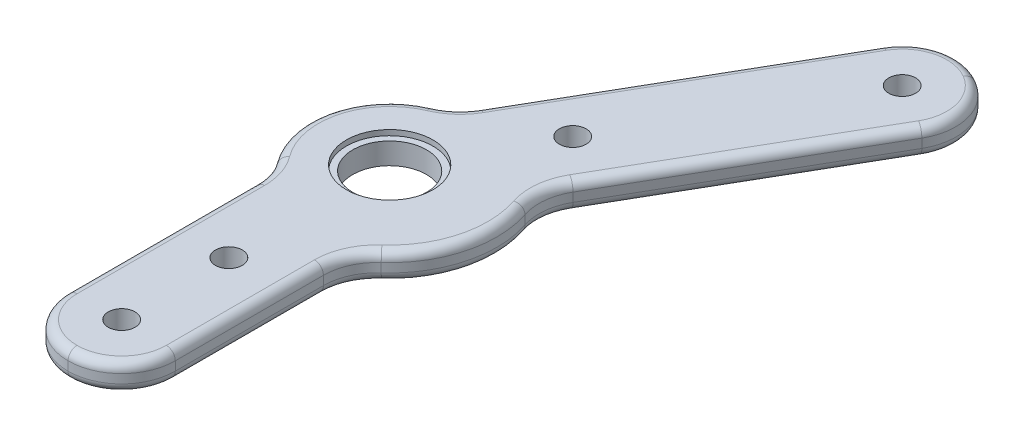
SolidWorks part; units mm, degrees
material "6061 Alloy"
ref_plane "Front Plane" through (0, 0, 0) normal (0, 0, 1) x (1, 0, 0)
ref_plane "Top Plane" through (0, 0, 0) normal (0, 1, 0) x (1, 0, 0)
ref_plane "Right Plane" through (0, 0, 0) normal (1, 0, 0) x (0, 0, -1)
sketch "Sketch1" plane through (0, 0, 0) normal (0, 1, 0) x (1, 0, 0)
  line L0 (0, 44.45) -> (0, -44.45) construction
  line L1 (-12.7, -44.45) -> (12.7, -44.45)
  line L2 (-12.7, -44.45) -> (-12.7, 31.75)
  line L3 (-12.7, 44.45) -> (12.7, 44.45) construction
  line L4 (12.7, -44.45) -> (12.7, 31.75)
  line L5 (-12.7, -44.45) -> (12.7, 44.45) construction
  line L6 (-12.7, 44.45) -> (12.7, -44.45) construction
  line L7 (0, 31.75) -> (50.8, 119.7382) construction
  line L8 (10.9985, 25.4) -> (61.7985, 113.3882)
  line L9 (61.7985, 113.3882) -> (39.8015, 126.0882)
  line L10 (39.8015, 126.0882) -> (-10.9985, 38.1)
  line L11 (-10.9985, 38.1) -> (10.9985, 25.4) construction
  line L12 (12.7, 44.45) -> (12.7, 31.75) construction
  line L13 (12.7, 44.45) -> (12.7, 79.147) construction
  circle A0 centre (0, 31.75) radius 12.7 construction
  circle A1 centre (0, -31.75) radius 3.175
  circle A2 centre (0, -6.35) radius 3.175
  circle A3 centre (0, 31.75) radius 8.7312
  circle A4 centre (44.45, 108.7397) radius 3.175
  circle A5 centre (15.875, 59.2463) radius 3.175
  circle A6 centre (0, 31.75) radius 19.05
  arc A7 (21.997, 44.45) -> (12.7, 9.753) centre (0, 31.75) cw
  point P0 (0, 0)
  point P16 (50.8, 119.7382)
  point P21 (0, 31.75)
  dimension "D4" = 12.7
  dimension "D1" = 6.35
  dimension "D7" = 88.9
  dimension "D8" = 12.7
  dimension "D9" = 17.4625
  dimension "D10" = 6.35
  dimension "D11" = 6.35
  dimension "D2" = 25.4
  dimension "D3" = 30
  dimension "D5" = 25.4
  dimension "D6" = 38.1
extrude "Boss-Extrude1" add sketch "Sketch1" along normal blind 6.35 contours A0 L2 L1 L4 L8 A2 A1 | A0 A3 | A0 L4 L8 L9 L10 A4 | A0 L8 L4 | L4 A6 L8 | A7 L8 A6 L4 region at (0, 0, 14.9202) region at (-17.8869, 0, -36.5428) region at (19.9726, 0, -26.3983) region at (29.7636, 0, -83.3021) region at (15.7679, 0, -27.525)
fillet "Fillet2" radius 12.7 8 edges at (39.8015, 3.175, -126.0882) (61.7985, 3.175, -113.3882) (-12.7, 3.175, 44.45) (12.7, 3.175, 44.45) (-3.899, 3.175, -50.3967) (-12.7, 3.175, -17.551) (12.7, 3.175, -9.753) (21.997, 3.175, -44.45)
fillet "Fillet3" radius 2.1167 28 edges at (12.7, 0, 14.199) (8.9803, 0, 40.7303) (-8.9803, 0, 40.7303) (-12.7, 0, 9.525) (15.989, 0, -84.8437) (41.163, 0, -121.0069) (56.7173, 0, -112.0267) (12.7, 6.35, 14.199) (8.9803, 6.35, 40.7303) (-8.9803, 6.35, 40.7303) (-12.7, 6.35, 9.525) (15.989, 6.35, -84.8437) (41.163, 6.35, -121.0069) (56.7173, 6.35, -112.0267) (40.323, 0, -76.1916) (40.323, 6.35, -76.1916) (-13.3517, 0, -16.7161) (-18.4009, 0, -36.6805) (-4.046, 0, -51.4456) (-13.3517, 6.35, -16.7161) (-18.4009, 6.35, -36.6805) (-4.046, 6.35, -51.4456) (23.5635, 0, -44.95) (24.5345, 0, -25.176) (13.8065, 0, -8.5367) (23.5635, 6.35, -44.95) (24.5345, 6.35, -25.176) (13.8065, 6.35, -8.5367)
sketch "Sketch2" plane through (0, 6.35, 0) normal (0, 1, 0) x (1, 0, 0)
  circle A0 centre (0, 31.75) radius 10.2489
  dimension "D1" = 20.4978
extrude "Cut-Extrude1" cut sketch "Sketch2" against normal blind 1.27
